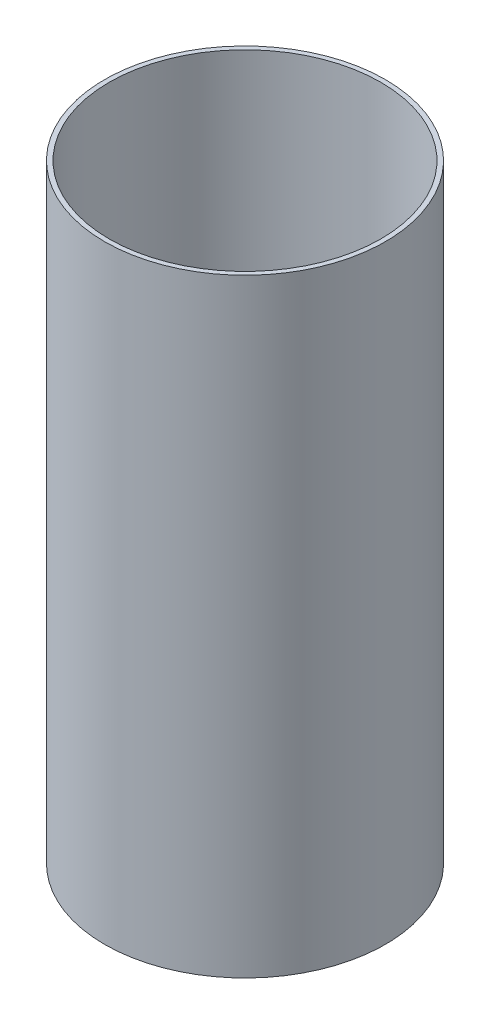
SolidWorks part; units mm, degrees
material "A-Glass Fiber"
ref_plane "Front Plane" through (0, 0, 0) normal (0, 0, 1) x (1, 0, 0)
ref_plane "Top Plane" through (0, 0, 0) normal (0, 1, 0) x (1, 0, 0)
ref_plane "Right Plane" through (0, 0, 0) normal (1, 0, 0) x (0, 0, -1)
sketch "Sketch1" plane through (0, 0, 0) normal (0, 1, 0) x (1, 0, 0)
  circle A0 centre (0, 0) radius 76.1746
  circle A1 centre (0, 0) radius 73.66
  dimension "D1" = 152.3492
  dimension "D2" = 147.32
extrude "Boss-Extrude1" add sketch "Sketch1" along normal blind 330.2
equation "\"Mid_Coupler_Length\" = 13in"
equation "\"D1@Boss-Extrude1\"=\"Mid_Coupler_Length\""
